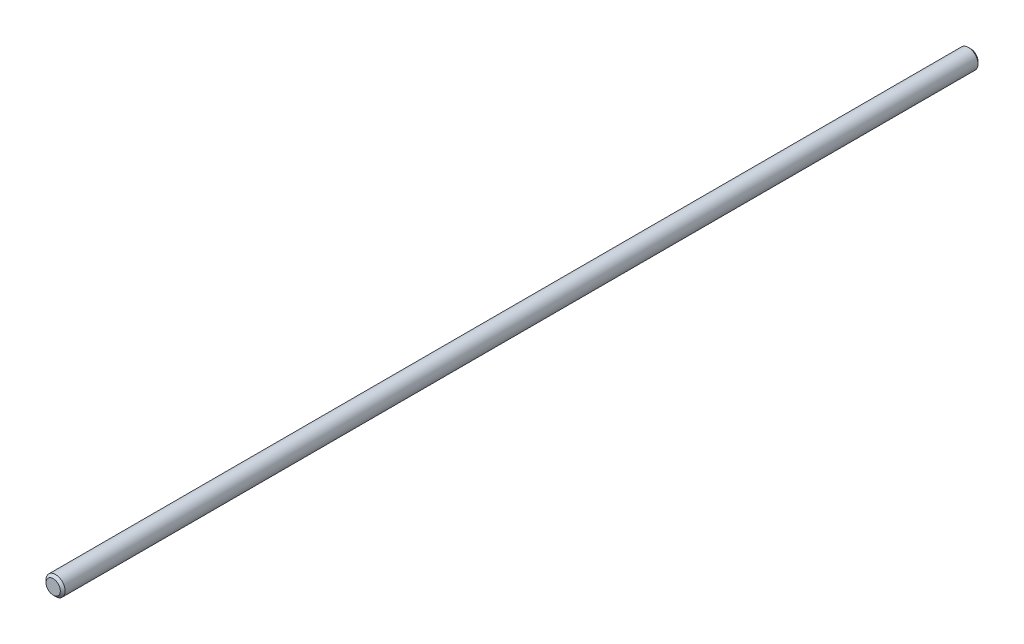
SolidWorks part; units mm, degrees
material "AISI 1020"
ref_plane "Front Plane" through (0, 0, 0) normal (0, 0, 1) x (1, 0, 0)
ref_plane "Top Plane" through (0, 0, 0) normal (0, 1, 0) x (1, 0, 0)
ref_plane "Right Plane" through (0, 0, 0) normal (1, 0, 0) x (0, 0, -1)
sketch "Sketch1" plane through (0, 0, 0) normal (1, 0, 0) x (0, 0, -1)
  line L1 (-228.6, 4.7625) -> (228.6, 4.7625)
  line L2 (-228.6, 4.7625) -> (-228.6, 0)
  line L3 (-228.6, 0) -> (228.6, 0) construction
  line L4 (228.6, 4.7625) -> (228.6, 0)
  point P4 (0, 0)
  point P5 (-227.0125, 4.7625)
  point P7 (-115.8875, 4.7625)
  point P8 (224.6313, 4.7625)
  point P9 (224.6313, -4.7625)
  dimension "Thread Diameter" = 9.525
  dimension "Length" = 457.2
  dimension "Thread Pitch" = 1.5875
  dimension "Segment Length" = 112.7125
  dimension "D1" = 3.9688
sketch "Sketch2" plane through (0, 0, 0) normal (1, 0, 0) x (0, 0, -1)
  line L1 (-228.6, 0) -> (228.6, 0)
  line L2 (-228.6, 0) -> (-228.6, 4.7625)
  line L3 (-228.6, 4.7625) -> (228.6, 4.7625)
  line L4 (228.6, 0) -> (228.6, 4.7625)
revolve "Revolve1" add sketch "Sketch2" angle 360 about L1
chamfer "Chamfer1" distance 1.1906 angle 45 2 edges at (4.7625, 0, -228.6) (4.7625, 0, 228.6)
sketch "Drawing Reference 1" plane through (0, 0, 0) normal (1, 0, 0) x (0, 0, -1)
  line L0 (-228.6, 4.7625) -> (228.6, 4.7625) construction
  line L1 (-228.6, 4.7625) -> (-228.6, 0) construction
  line L2 (228.6, 4.7625) -> (228.6, 0) construction
  point P0 (-221.4562, 4.7625)
  point P1 (221.4563, 4.7625)
  dimension "D1" = 7.1437
  dimension "D2" = 7.1437
sketch "Sketch3" plane through (0, 0, -228.6) normal (0, 0, -1) x (-1, 0, 0)
  circle A0 centre (0, 0) radius 4.7625 construction
  circle A1 centre (0, 0) radius 4.7625
curve "Helix/Spiral1" pitch 1.5875 height 114.3 turns 72
sketch "Sketch4" plane through (0, 0, 0) normal (1, 0, 0) x (0, 0, -1)
  line L0 (228.5008, 4.9344) -> (229.2945, 3.5595) construction
  line L1 (229.2945, 3.5595) -> (230.0883, 4.9344) construction
  line L2 (230.0883, 4.9344) -> (228.5008, 4.9344) construction
  line L3 (228.5504, 4.8484) -> (230.0387, 4.8484)
  line L4 (230.0387, 4.8484) -> (229.3937, 3.7314)
  line L5 (229.3937, 3.7314) -> (229.1953, 3.7314)
  line L6 (229.1953, 3.7314) -> (228.5504, 4.8484)
  line L7 (229.2945, 3.7314) -> (229.2945, 3.5595) construction
  line L8 (228.6, 4.7625) -> (229.9891, 4.7625) construction
  line L9 (229.2945, 4.9344) -> (229.2945, 4.7625) construction
  point P12 (229.2945, 4.8484)
  dimension "D1" = 1.5875
  dimension "D2" = 0.1984
sweep "Cut-Sweep1" [suppressed] cut profiles "Sketch4" path "Helix/Spiral1"
pattern_linear "LPattern1" [suppressed] of bodies 105
equation "\"D1@Chamfer1\"=0.75*\"Thread Pitch@Sketch1\""
equation "\"Segment Length@Sketch1\"=\"Thread Pitch@Sketch1\"*71"
equation "\"D4@Helix/Spiral1\"=\"Thread Pitch@Sketch1\""
equation "\"D5@Helix/Spiral1\"=(\"Segment Length@Sketch1\"/\"Thread Pitch@Sketch1\")+1"
equation "\"D2@Sketch4\"=\"D1@Sketch4\"/8"
equation "\"D1@Sketch4\"=\"Thread Pitch@Sketch1\""
equation "\"D3@LPattern1\"=\"Segment Length@Sketch1\""
equation "\"D1@Drawing Reference 1\"=\"Thread Diameter@Sketch1\"*0.75"
equation "\"D2@Drawing Reference 1\" = \"D1@Drawing Reference 1\""
equation "\"D1@Sketch1\"=2.5*\"Thread Pitch@Sketch1\""
